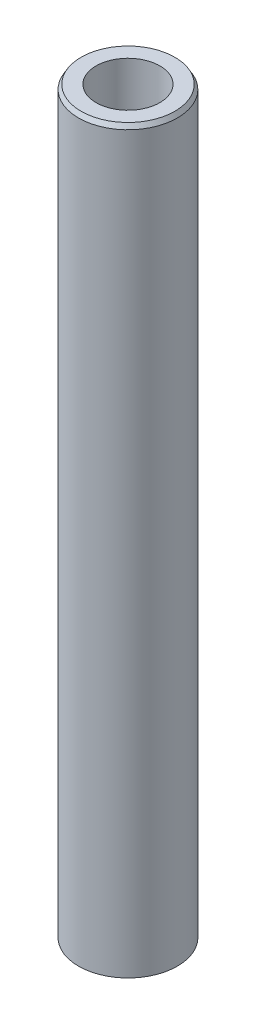
SolidWorks part; units mm, degrees
ref_plane "Front Plane" through (0, 0, 0) normal (0, 0, 1) x (1, 0, 0)
ref_plane "Top Plane" through (0, 0, 0) normal (0, 1, 0) x (1, 0, 0)
ref_plane "Right Plane" through (0, 0, 0) normal (1, 0, 0) x (0, 0, -1)
sketch "Sketch1" plane through (0, 0, 0) normal (0, 1, 0) x (1, 0, 0)
  circle A0 centre (0, 0) radius 40
  dimension "SHAFT_OD" = 80
extrude "Boss-Extrude1" add sketch "Sketch1" along normal blind 600
sketch "Sketch2" plane through (0, 0, 0) normal (0, 1, 0) x (1, 0, 0)
  circle A0 centre (0, 0) radius 25.7956
  dimension "BORE_D" = 51.5912
extrude "Cut-Extrude1" cut sketch "Sketch2" along normal through all
chamfer "Chamfer1" distance 3.6302 angle 30 2 edges at (0, 600, 40) (0, 0, 40) first distance on face at (0, 600, 40) first distance on face at (0, 0, 25.7956)
